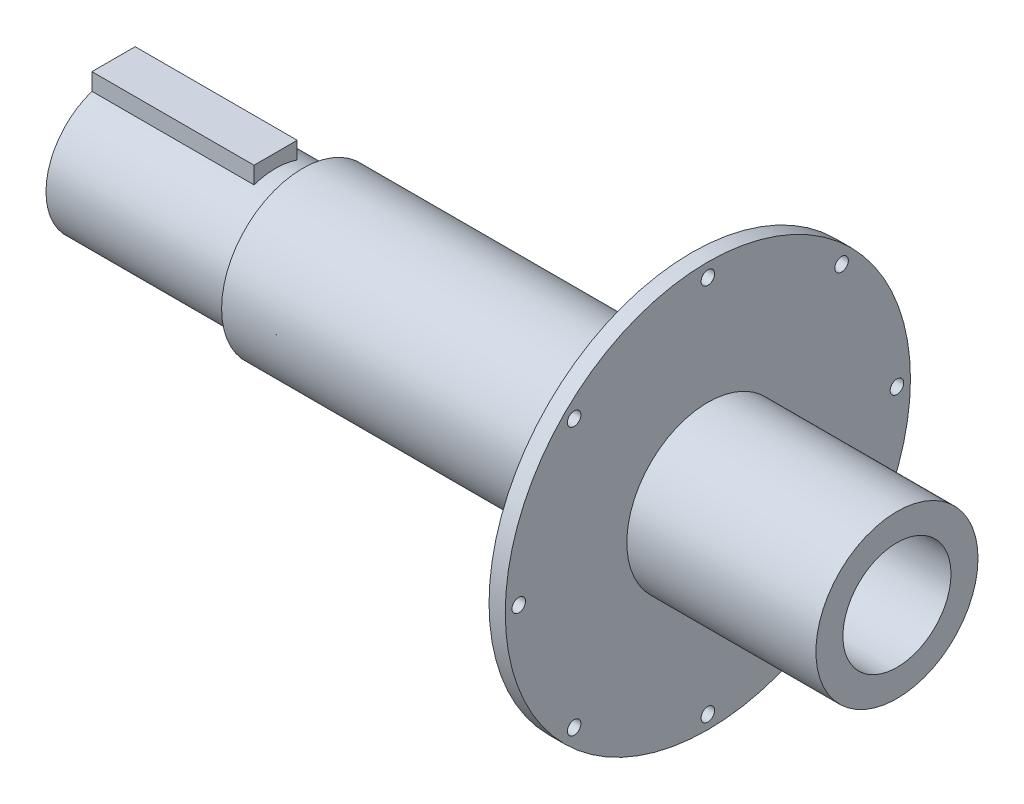
SolidWorks part; units mm, degrees
ref_plane "Front Plane" through (0, 0, 0) normal (0, 0, 1) x (1, 0, 0)
ref_plane "Top Plane" through (0, 0, 0) normal (0, 1, 0) x (1, 0, 0)
ref_plane "Right Plane" through (0, 0, 0) normal (1, 0, 0) x (0, 0, -1)
sketch "Sketch1" plane through (0, 0, 0) normal (1, 0, 0) x (0, 0, -1)
  circle A0 centre (0, 0) radius 10
  circle A1 centre (0, 0) radius 15
  circle A2 centre (0, 0) radius 25
  circle A3 centre (0, 0) radius 37.5
  dimension "D1" = 50
  dimension "D2" = 30
  dimension "D3" = 20
  dimension "D4" = 75
extrude "Boss-Extrude1" add sketch "Sketch1" against normal blind 3 contours A1 A0 | A2 A1 region at (0, 0, 14.5757) region at (0, 0, 24.2929)
extrude "Boss-Extrude2" add sketch "Sketch1<3>" along normal blind 35 and the other way blind 110 separate body contours A1 A0 region at (0, 0, 14.5757)
sketch "Sketch1<3>" plane through (0, 0, 0) normal (1, 0, 0) x (0, 0, -1) same geometry as "Sketch1"
extrude "Boss-Extrude3" add sketch "Sketch1<4>" against normal blind 3 contours A3 A2 region at (0, 0, 36.4393)
sketch "Sketch1<4>" plane through (0, 0, 0) normal (1, 0, 0) x (0, 0, -1) same geometry as "Sketch1"
hole_wizard "M3 Tapped Hole1" positions "Sketch2" profile "Sketch3" tap size "M3" standard "ISO" end condition through all
sketch "Sketch2" plane through (-3, 0, 0) normal (-1, 0, 0) x (0, 0, 1)
  line L0 (0, 0) -> (0, -37.5) construction
  line L1 (0, -37.5) -> (0, 37.5) construction
  line L2 (0, 37.5) -> (0, 0) construction
  line L3 (0, 0) -> (37.5, 0) construction
  line L4 (37.5, 0) -> (-37.5, 0) construction
  line L5 (-37.5, 0) -> (0, 0) construction
  line L6 (0, 0) -> (-26.5165, -26.5165) construction
  line L7 (-26.5165, -26.5165) -> (26.5165, 26.5165) construction
  line L8 (26.5165, 26.5165) -> (0, 0) construction
  line L9 (0, 0) -> (26.5165, -26.5165) construction
  line L10 (26.5165, -26.5165) -> (-26.5165, 26.5165) construction
  circle A0 centre (0, 0) radius 37.5 construction
  circle A1 centre (0, 0) radius 35
  point P0 (35, 0)
  point P2 (0, 35)
  point P4 (-35, 0)
  point P6 (0, -35)
  point P8 (24.7487, 24.7487)
  point P10 (-24.7487, 24.7487)
  point P12 (-24.7487, -24.7487)
  point P14 (24.7487, -24.7487)
  dimension "D1" = 70
sketch "Sketch3" plane through (-3, 0, 35) normal (0, 1, 0) x (0, 0, 1)
  line L0 (0, 0) -> (0, 38)
  line L1 (0, 38) -> (1.25, 38)
  line L2 (1.25, 38) -> (1.25, 0.275)
  line L3 (1.25, 0.275) -> (1.525, 0)
  line L5 (1.525, 0) -> (0, 0)
  line L6 (-1.25, 0.275) -> (-1.525, 0) construction
  line L11 (0, -6.35) -> (0, 107.95) construction
  dimension "Thru Tap Drill Dia." = 2.5
  dimension "Thru Tap Drill Depth" = 38
  dimension "Near C'Sink Dia." = 3.05
  dimension "Near C'Sink Angle" = 90
cosmetic thread "Hole Thread1" parameters "D1"=3, "D2"=3.5
cosmetic thread "Hole Thread2" parameters "D1"=3, "D2"=3.5
cosmetic thread "Hole Thread3" parameters "D1"=3, "D2"=3.5
cosmetic thread "Hole Thread4" parameters "D1"=3, "D2"=3.5
cosmetic thread "Hole Thread5" parameters "D1"=3, "D2"=3.5
cosmetic thread "Hole Thread6" parameters "D1"=3, "D2"=3.5
cosmetic thread "Hole Thread7" parameters "D1"=3, "D2"=3.5
cosmetic thread "Hole Thread8" parameters "D1"=3, "D2"=3.5
ref_plane "Plane1" through (-110, 0, 0) normal (-1, 0, 0) x (0, 0, 1)
sketch "Sketch4" plane through (-110, 0, 0) normal (-1, 0, 0) x (0, 0, 1)
  line L1 (-4, 15) -> (4, 15)
  line L2 (-4, 15) -> (-4, -15)
  line L3 (-4, -15) -> (4, -15)
  line L4 (4, 15) -> (4, -15)
  line L5 (-4, 15) -> (4, -15) construction
  line L6 (-4, -15) -> (4, 15) construction
  circle A0 centre (0, 0) radius 12.5
  circle A1 centre (0, 0) radius 20
  dimension "D1" = 25
  dimension "D2" = 40
  dimension "D3" = 30
  dimension "D4" = 8
extrude "Cut-Extrude1" cut sketch "Sketch4" against normal blind 35 contours A1 A0 L2 L1 L4 L3 | A0 L4 L1 L2 | A0 L2 L3 L4 region at (-110, 13.6346, 0) region at (-110, -13.6346, 0) region at (-110, 0, -19.4343)
extrude "Boss-Extrude4" add sketch "Sketch4<3>" against normal blind 30 contours A0 L4 L1 L2 | L4 A0 | L4 A0 L2 | L2 A0 region at (-110, 13.6346, 0) region at (-110, 0, 0) region at (-110, 0, -7.5239) region at (-110, 0, 7.5239)
sketch "Sketch4<3>" plane through (-110, 0, 0) normal (-1, 0, 0) x (0, 0, 1) same geometry as "Sketch4"
